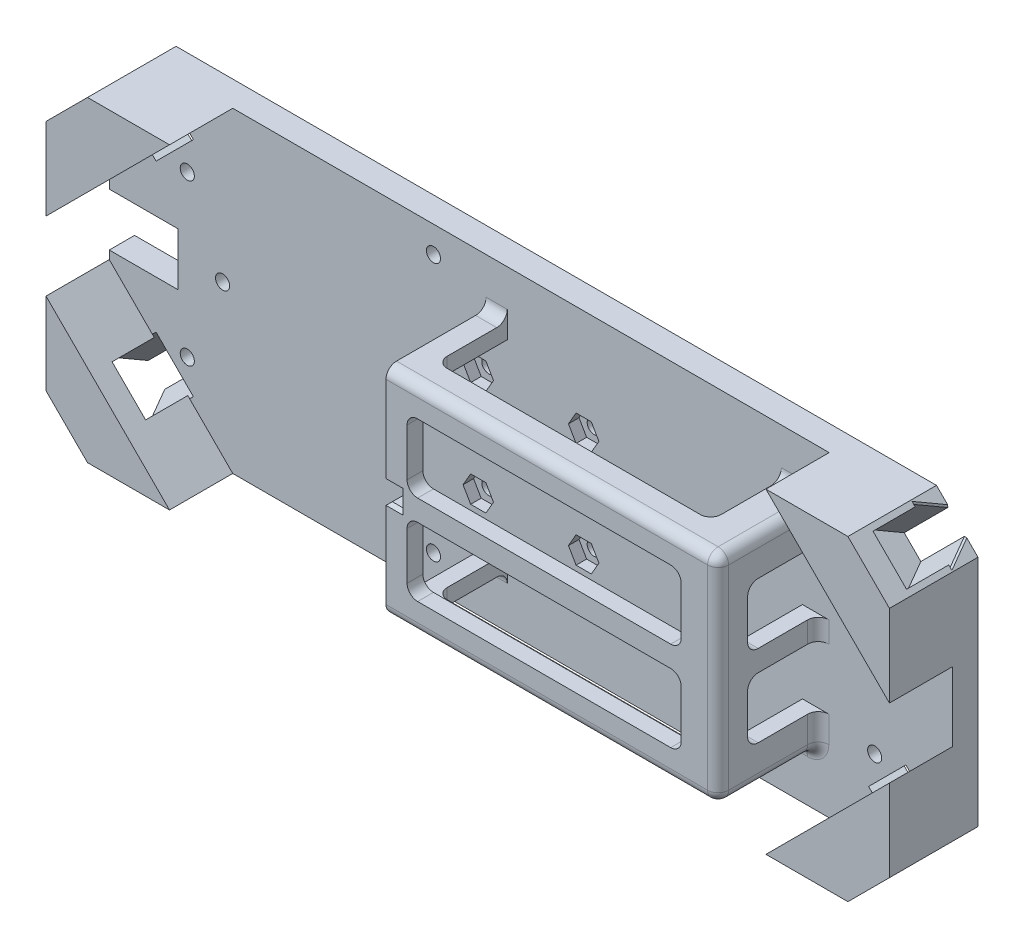
SolidWorks part; units mm, degrees
ref_plane "Front Plane" through (0, 0, 0) normal (0, 0, 1) x (1, 0, 0)
ref_plane "Top Plane" through (0, 0, 0) normal (0, 1, 0) x (1, 0, 0)
ref_plane "Right Plane" through (0, 0, 0) normal (1, 0, 0) x (0, 0, -1)
sketch "Sketch1" plane through (10.8587, 0, 0) normal (0, 0, 1) x (1, 0, 0)
  line L0 (-52.705, 21.59) -> (48.895, 21.59)
  line L1 (52.705, -25.4) -> (-52.705, -25.4)
  line L2 (52.705, -25.4) -> (52.705, 25.4)
  line L3 (52.705, 25.4) -> (-52.705, 25.4)
  line L4 (-52.705, -25.4) -> (-52.705, 25.4)
  line L5 (52.705, -25.4) -> (-52.705, 25.4) construction
  line L6 (52.705, 25.4) -> (-52.705, -25.4) construction
  line L7 (48.895, 21.59) -> (48.895, -22.86)
  line L8 (48.895, -22.86) -> (-52.705, -22.86)
  line L9 (-52.705, 13.97) -> (-6.985, 13.97)
  line L10 (-6.985, 13.97) -> (-6.985, -6.35)
  line L11 (-6.985, -6.35) -> (-52.705, -6.35)
  point P0 (0, 0)
  dimension "D1" = 105.41
  dimension "D2" = 50.8
  dimension "D3" = 101.6
  dimension "D4" = 44.45
  dimension "D5" = 3.81
  dimension "D6" = 45.72
  dimension "D7" = 20.32
  dimension "D8" = 7.62
extrude "Boss-Extrude1" add sketch "Sketch1" along normal blind 27.432 contours L7 L8 L4 L1 L2 L3 L0 region at (-40.6761, 23.495, 0)
extrude "Boss-Extrude2" add sketch "Sketch1<3>" along normal blind 5.08 contours L10 L11 L4 L8 L7 L0 L9 region at (16.19, -1.7862, 0)
sketch "Sketch1<3>" plane through (10.8587, 0, 0) normal (0, 0, 1) x (1, 0, 0) same geometry as "Sketch1"
sketch "Sketch4" plane through (10.8587, 0, 5.08) normal (0, 0, 1) x (1, 0, 0)
  line L0 (-52.705, 21.59) -> (48.895, 21.59) construction
  line L1 (-44.7859, 21.59) -> (-47.9241, 21.59)
  line L2 (-47.9241, 21.59) -> (-49.4932, 18.8722)
  line L3 (-49.4932, 18.8722) -> (-47.9241, 16.1544)
  line L4 (-47.9241, 16.1544) -> (-44.7859, 16.1544)
  line L5 (-44.7859, 16.1544) -> (-43.2168, 18.8722)
  line L6 (-43.2168, 18.8722) -> (-44.7859, 21.59)
  line L7 (-52.705, 13.97) -> (-52.705, 21.59) construction
  line L8 (-13.3987, 22.7847) -> (-13.3987, -11.3368) construction
  line L9 (21.1266, 16.1544) -> (17.9884, 16.1544)
  line L10 (17.9884, 16.1544) -> (16.4193, 18.8722)
  line L11 (16.4193, 18.8722) -> (17.9884, 21.59)
  line L12 (17.9884, 21.59) -> (21.1266, 21.59)
  line L13 (21.1266, 21.59) -> (22.6958, 18.8722)
  line L14 (22.6958, 18.8722) -> (21.1266, 16.1544)
  line L15 (0, 0) -> (10.9329, 0) construction
  line L16 (22.6958, -18.8722) -> (21.1266, -16.1544)
  line L17 (21.1266, -21.59) -> (22.6958, -18.8722)
  line L18 (17.9884, -21.59) -> (21.1266, -21.59)
  line L19 (16.4193, -18.8722) -> (17.9884, -21.59)
  line L20 (17.9884, -16.1544) -> (16.4193, -18.8722)
  line L21 (21.1266, -16.1544) -> (17.9884, -16.1544)
  line L22 (-49.4932, -18.8722) -> (-47.9241, -16.1544)
  line L23 (-47.9241, -21.59) -> (-49.4932, -18.8722)
  line L24 (-43.2168, -18.8722) -> (-44.7859, -21.59)
  line L25 (-44.7859, -16.1544) -> (-43.2168, -18.8722)
  line L26 (-47.9241, -16.1544) -> (-44.7859, -16.1544)
  line L27 (-44.7859, -21.59) -> (-47.9241, -21.59)
  circle A0 centre (-46.355, 18.8722) radius 2.7178 construction
  circle A1 centre (-46.355, 18.8722) radius 1.524
  circle A2 centre (19.5575, 18.8722) radius 1.524
  circle A3 centre (-46.355, -18.8722) radius 1.524
  circle A4 centre (19.5575, -18.8722) radius 1.524
  dimension "D4" = 3.048
  dimension "D1" = 5.4356
  dimension "D2" = 6.35
  dimension "D3" = 2.54
extrude "Cut-Extrude1" cut sketch "Sketch4" against normal blind 2.286 contours L5 L6 L14 L2 L3 L4 A1 | L14 L13 L11 L10 L9 A2 | L26 L22 L23 L12 L24 L25 A3 | L16 L21 L20 L19 L12 L17 A4 region at (-33.2145, 20.1896, 5.08) region at (30.4163, 16.2374, 5.08) region at (32.698, -20.1896, 5.08) region at (-37.778, -17.5548, 5.08)
extrude "Cut-Extrude2" cut sketch "Sketch4<4>" against normal through all contours A1 | A2 | A3 | A4 region at (-35.4963, 18.8722, 5.08) region at (30.4163, 18.8722, 5.08) region at (-35.4963, -18.8722, 5.08) region at (30.4163, -18.8722, 5.08)
sketch "Sketch4<4>" plane through (10.8587, 0, 5.08) normal (0, 0, 1) x (1, 0, 0) same geometry as "Sketch4"
sketch "Sketch7" plane through (10.8587, 0, 27.432) normal (0, 0, 1) x (1, 0, 0)
  line L0 (0, 0) -> (-46.355, 0) construction
  line L1 (-52.705, 25.4) -> (52.705, 25.4)
  line L2 (-52.705, 25.4) -> (-52.705, 6.35)
  line L3 (-52.705, -25.4) -> (52.705, -25.4)
  line L4 (52.705, 25.4) -> (52.705, -25.4)
  line L5 (-52.705, 6.35) -> (-46.355, 6.35)
  line L7 (-52.705, -6.35) -> (-46.355, -6.35)
  line L8 (-46.355, 6.35) -> (-46.355, -6.35)
  line L9 (-52.705, -6.35) -> (-52.705, -25.4)
  line L10 (-28.575, 0) -> (-1035.3573, 0) construction
  point P11 (-46.355, 0)
  dimension "D1" = 12.7
  dimension "D2" = 6.35
extrude "Boss-Extrude3" add sketch "Sketch7" along normal blind 3.81
fillet "Fillet1" radius 2.54 5 edges at (10.8587, -25.4, 31.242) (63.5637, -25.4, 15.621) (63.5637, 0, 31.242) (63.5637, 25.4, 15.621) (10.8587, 25.4, 31.242)
chamfer "Chamfer3" distance 1.27 angle 45 9 edges at (-41.8463, 21.59, 16.256) (-41.8463, -22.86, 16.256) (-41.8463, 13.97, 27.432) (-41.8463, -14.605, 27.432) (-41.8463, -6.35, 29.337) (-38.6713, -6.35, 31.242) (-35.4963, 0, 31.242) (-38.6713, 6.35, 31.242) (-41.8463, 6.35, 29.337)
chamfer "Chamfer4" distance 0.254 angle 45 4 edges at (-33.9723, -18.8722, 0) (31.9403, -18.8722, 0) (-33.9723, 18.8722, 0) (31.9403, 18.8722, 0)
sketch "Sketch8" plane through (10.8587, 0, 5.08) normal (0, 0, 1) x (1, 0, 0)
  line L0 (-52.705, -7.62) -> (-52.705, -22.86) construction
  line L1 (48.895, 21.59) -> (-52.705, 21.59)
  line L2 (48.895, 21.59) -> (48.895, -22.86)
  line L3 (48.895, -22.86) -> (-52.705, -22.86)
  line L4 (-52.705, 21.59) -> (-52.705, -22.86)
  line L5 (48.895, -22.86) -> (-51.435, -22.86) construction
extrude "Cut-Extrude3" cut sketch "Sketch8" against normal up to surface (5.08 mm away) up to face at (-33.7183, -18.8722, 0)
chamfer "Chamfer5" distance 1.27 angle 45 2 edges at (-41.8463, -22.86, 2.54) (-41.8463, 21.59, 2.54)
sketch "Sketch9" plane through (10.8587, 0, 0) normal (0, 0, -1) x (-1, 0, 0)
  line L0 (-90.7413, 28.1) -> (-80.7413, 38.1)
  line L1 (-80.7413, -38.1) -> (102.4587, -38.1)
  line L2 (-90.7413, -28.1) -> (-90.7413, 28.1)
  line L3 (-80.7413, 38.1) -> (102.4587, 38.1)
  line L4 (112.4587, -28.1) -> (112.4587, 28.1)
  line L5 (-90.7413, -38.1) -> (112.4587, 38.1) construction
  line L6 (-90.7413, 38.1) -> (112.4587, -38.1) construction
  line L7 (-90.7413, -28.1) -> (-80.7413, -38.1)
  line L8 (102.4587, 38.1) -> (112.4587, 28.1)
  line L9 (102.4587, -38.1) -> (112.4587, -28.1)
  point P0 (10.8587, 0)
  dimension "D1" = 203.2
  dimension "D2" = 76.2
extrude "Boss-Extrude4" add sketch "Sketch9" along normal blind 6.096
fillet "Fillet2" radius 1.27 5 edges at (9.5887, -25.4, 0) (62.8198, -24.6561, 0) (63.5637, 0, 0) (62.8198, 24.6561, 0) (9.5887, 25.4, 0)
sketch "Sketch11" plane through (0, 0, 0) normal (0, 0, 1) x (1, 0, 0)
  line L0 (-101.6, 28.1) -> (-91.6, 38.1)
  line L1 (-91.6, 38.1) -> (-84.9257, 38.1)
  line L4 (-101.6, -28.1) -> (-101.6, 28.1) construction
  line L5 (-101.6, 21.4257) -> (-101.6, 28.1)
  line L6 (0, 0) -> (0, 53.0626) construction
  line L7 (-1000, 0) -> (0, 0) construction
  line L25 (-76.5885, 29.7628) -> (-93.2628, 13.0885)
  line L26 (-84.9257, 38.1) -> (-76.5885, 29.7628)
  line L28 (-101.6, 21.4257) -> (-93.2628, 13.0885)
  line L54 (0, -17.1831) -> (0, 17.1831) construction
  line L55 (84.9257, 38.1) -> (76.5885, 29.7628)
  line L56 (91.6, 38.1) -> (84.9257, 38.1)
  line L57 (101.6, 28.1) -> (91.6, 38.1)
  line L58 (101.6, 21.4257) -> (101.6, 28.1)
  line L59 (101.6, 21.4257) -> (93.2628, 13.0885)
  line L60 (76.5885, 29.7628) -> (93.2628, 13.0885)
  line L61 (17.1831, 0) -> (-17.1831, 0) construction
  line L62 (91.6, -38.1) -> (84.9257, -38.1)
  line L63 (101.6, -28.1) -> (91.6, -38.1)
  line L64 (101.6, -21.4257) -> (101.6, -28.1)
  line L65 (101.6, -21.4257) -> (93.2628, -13.0885)
  line L66 (76.5885, -29.7628) -> (93.2628, -13.0885)
  line L67 (84.9257, -38.1) -> (76.5885, -29.7628)
  line L68 (-84.9257, -38.1) -> (-76.5885, -29.7628)
  line L69 (-91.6, -38.1) -> (-84.9257, -38.1)
  line L70 (-101.6, -28.1) -> (-91.6, -38.1)
  line L71 (-101.6, -21.4257) -> (-101.6, -28.1)
  line L72 (-101.6, -21.4257) -> (-93.2628, -13.0885)
  line L73 (-76.5885, -29.7628) -> (-93.2628, -13.0885)
  dimension "D1" = 16.51
  dimension "D2" = 8.3372
extrude "Boss-Extrude5" [suppressed] add sketch "Sketch11" along normal blind 19.05
sketch "Sketch13" plane through (-64.85, 64.85, 0) normal (-0.7071, 0.7071, 0) x (0, 0, 1)
  line L0 (-6.096, -44.9013) -> (-6.096, -42.0708)
  line L1 (-6.096, -51.9723) -> (-6.096, -37.8302) construction
  line L2 (-6.096, -42.0708) -> (0, -38.5513)
  line L3 (0, -38.5513) -> (0, -51.2513)
  line L4 (0, -51.2513) -> (-6.096, -47.7318)
  line L5 (-6.096, -47.7318) -> (-6.096, -44.9013)
  dimension "D1" = 6.096
  dimension "D2" = 120
  dimension "D3" = 120
  dimension "D4" = 12.7
extrude "Cut-Extrude4" cut sketch "Sketch13" against normal blind 15.24
mirror "Mirror2" about plane through (0, 0, 0) normal (0, 1, 0) of "Cut-Extrude4"
mirror "Mirror3" about plane through (0, 0, 0) normal (1, 0, 0) of "Cut-Extrude4", "Mirror2"
chamfer "Chamfer7" distance 0.381 angle 45 8 edges at (99.8458, -29.8542, -3.048) (93.3542, -36.3458, -3.048) (93.3542, 36.3458, -3.048) (99.8458, 29.8542, -3.048) (-93.3542, 36.3458, -3.048) (-99.8458, 29.8542, -3.048) (-93.3542, -36.3458, -3.048) (-99.8458, -29.8542, -3.048)
sketch "Sketch17" [suppressed] plane through (0, 0, 19.05) normal (0, 0, 1) x (1, 0, 0)
  line L0 (-96.6, 33.1) -> (-92.1099, 37.5901)
  line L1 (-91.6, 38.1) -> (-101.6, 28.1) construction
  line L3 (20.6756, 0) -> (-20.6756, 0) construction
  line L6 (-80.4355, -25.9158) -> (-89.4158, -16.9355)
  line L8 (-101.0901, 28.6099) -> (-96.6, 33.1)
  line L10 (-92.1099, -37.5901) -> (-80.4355, -25.9158)
  line L30 (-92.1099, 37.5901) -> (-80.4355, 25.9158)
  line L31 (-93.2628, 13.0885) -> (-76.5885, 29.7628) construction
  line L32 (-80.4355, 25.9158) -> (-89.4158, 16.9355)
  line L33 (-89.4158, 16.9355) -> (-101.0901, 28.6099)
  line L34 (-96.6, -33.1) -> (-92.1099, -37.5901)
  line L35 (-101.0901, -28.6099) -> (-96.6, -33.1)
  line L36 (-89.4158, -16.9355) -> (-101.0901, -28.6099)
  line L37 (0, -20.6756) -> (0, 20.6756) construction
  line L38 (92.1099, -37.5901) -> (80.4355, -25.9158)
  line L39 (96.6, -33.1) -> (92.1099, -37.5901)
  line L40 (101.0901, -28.6099) -> (96.6, -33.1)
  line L41 (89.4158, -16.9355) -> (101.0901, -28.6099)
  line L42 (80.4355, -25.9158) -> (89.4158, -16.9355)
  line L43 (80.4355, 25.9158) -> (89.4158, 16.9355)
  line L44 (92.1099, 37.5901) -> (80.4355, 25.9158)
  line L45 (96.6, 33.1) -> (92.1099, 37.5901)
  line L46 (101.0901, 28.6099) -> (96.6, 33.1)
  line L47 (89.4158, 16.9355) -> (101.0901, 28.6099)
  dimension "D1" = 12.7
extrude "Cut-Extrude7" [suppressed] cut sketch "Sketch17" against normal blind 10.922
sketch "Sketch18" [suppressed] plane through (0, 0, 8.128) normal (0, 0, 1) x (1, 0, 0)
  line L0 (-92.1099, 37.5901) -> (-101.0901, 28.6099) construction
  line L1 (-80.4355, 25.9158) -> (-92.1099, 37.5901) construction
  circle A0 centre (-89.4158, 25.9158) radius 1.778
  dimension "D1" = 3.556
  dimension "D2" = 10.16
  dimension "D3" = 6.35
extrude "Cut-Extrude8" [suppressed] cut sketch "Sketch18" against normal up to surface (8.382 mm away) up to face at (0, 0, 0)
mirror "Mirror6" [suppressed] about plane through (0, 0, 0) normal (0, 1, 0)
mirror "Mirror7" [suppressed] about plane through (0, 0, 0) normal (1, 0, 0)
sketch "Sketch19" plane through (0, 0, 31.242) normal (0, 0, 1) x (1, 0, 0)
  line L1 (-67.9348, -33.6729) -> (67.9348, -33.6729)
  line L2 (-67.9348, -33.6729) -> (-67.9348, 33.6729)
  line L3 (-67.9348, 33.6729) -> (67.9348, 33.6729)
  line L4 (67.9348, -33.6729) -> (67.9348, 33.6729)
  line L5 (-67.9348, -33.6729) -> (67.9348, 33.6729) construction
  line L6 (-67.9348, 33.6729) -> (67.9348, -33.6729) construction
  point P0 (0, 0)
extrude "Cut-Extrude9" cut sketch "Sketch19" against normal up to surface (31.242 mm away) up to face at (0, 0, 0)
sketch "Sketch20" plane through (0, 0, 0) normal (0, 0, 1) x (1, 0, 0)
  line L0 (65.405, 22.86) -> (65.405, -21.59)
  line L1 (65.405, -21.59) -> (-10.795, -21.59)
  line L2 (65.405, 22.86) -> (-10.795, 22.86)
  line L3 (-10.795, 22.86) -> (-10.795, 26.67)
  line L4 (-10.795, 26.67) -> (69.215, 26.67)
  line L5 (69.215, 26.67) -> (69.215, -25.4)
  line L6 (69.215, -25.4) -> (-10.795, -25.4)
  line L7 (-10.795, -25.4) -> (-10.795, -21.59)
  line L8 (101.6, 28.1) -> (101.6, -28.1) construction
  line L9 (91.6, -38.1) -> (-91.6, -38.1) construction
  dimension "D1" = 52.07
  dimension "D2" = 44.45
  dimension "D3" = 3.81
  dimension "D4" = 80.01
  dimension "D5" = 76.2
  dimension "D6" = 32.385
  dimension "D7" = 12.7
extrude "Boss-Extrude6" add sketch "Sketch20" along normal blind 20.32
sketch "Sketch21" plane through (0, 0, 20.32) normal (0, 0, 1) x (1, 0, 0)
  line L1 (-10.795, 26.67) -> (69.215, 26.67)
  line L2 (-10.795, 26.67) -> (-10.795, -25.4)
  line L3 (-10.795, -25.4) -> (69.215, -25.4)
  line L4 (69.215, 26.67) -> (69.215, -25.4)
extrude "Boss-Extrude7" add sketch "Sketch21" along normal blind 3.81
fillet "Fillet3" radius 2.54 8 edges at (29.21, 26.67, 0) (69.215, 0.635, 0) (29.21, 26.67, 24.13) (69.215, 26.67, 12.065) (69.215, 0.635, 24.13) (69.215, -25.4, 12.065) (29.21, -25.4, 0) (29.21, -25.4, 24.13)
chamfer "Chamfer8" distance 1.27 angle 45 3 edges at (-10.795, -21.59, 10.16) (-10.795, 22.86, 10.16) (-10.795, 0.635, 20.32)
chamfer "Chamfer9" [suppressed] distance 0.254 angle 45
sketch "Sketch22" [suppressed] plane through (0, 0, -0.254) normal (0, 0, -1) x (-1, 0, 0)
  line L0 (-91.6432, -38.0568) -> (-101.5568, -28.1432) construction
  line L1 (-85.0164, -25.9158) -> (-87.2161, -22.1058)
  line L2 (-87.2161, -22.1058) -> (-91.6155, -22.1058)
  line L3 (-91.6155, -22.1058) -> (-93.8152, -25.9158)
  line L4 (-93.8152, -25.9158) -> (-91.6155, -29.7258)
  line L5 (-91.6155, -29.7258) -> (-87.2161, -29.7258)
  line L6 (-87.2161, -29.7258) -> (-85.0164, -25.9158)
  circle A0 centre (-89.4158, -25.9158) radius 3.81 construction
  circle A1 centre (-89.4158, -25.9158) radius 1.778 construction
  dimension "D1" = 7.62
  dimension "D2" = 10.16
  dimension "D3" = 0
extrude "Cut-Extrude10" [suppressed] cut sketch "Sketch22" against normal blind 3.302
mirror "Mirror8" [suppressed] about plane through (0, 0, 0) normal (0, 1, 0)
mirror "Mirror9" [suppressed] about plane through (0, 0, 0) normal (1, 0, 0)
sketch "Sketch23" plane through (0, 0, 0) normal (0, 0, 1) x (1, 0, 0)
  line L16 (90.3138, -17.8336) -> (100.8207, -28.3405)
  line L18 (-91.6, -38.1) -> (91.6, -38.1)
  line L19 (100.8207, -28.3405) -> (101.4012, -28.2988)
  line L20 (100.8207, -28.3405) -> (101.4012, -28.2988)
  line L21 (101.4012, -28.2988) -> (101.6, -28.1)
  line L22 (101.6, -28.1) -> (101.6, 28.1)
  line L23 (101.4012, -28.2988) -> (101.6, -28.1)
  line L24 (101.6, 28.1) -> (101.4012, 28.2988)
  line L25 (101.6, 28.1) -> (101.4012, 28.2988)
  line L26 (91.6, 38.1) -> (-91.6, 38.1)
  line L27 (101.4012, 28.2988) -> (100.8207, 28.3405)
  line L28 (101.4012, 28.2988) -> (100.8207, 28.3405)
  line L29 (90.3138, -17.8336) -> (100.8207, -28.3405)
  line L30 (-101.6, 28.1) -> (-101.6, -28.1)
  line L34 (-91.6, -38.1) -> (91.6, -38.1)
  line L38 (101.6, -28.1) -> (101.6, 28.1)
  line L42 (91.6, 38.1) -> (-91.6, 38.1)
  line L46 (-101.6, 28.1) -> (-101.6, -28.1)
  line L56 (91.8405, 37.3207) -> (91.7988, 37.9012)
  line L57 (91.8405, 37.3207) -> (91.7988, 37.9012)
  line L58 (91.7988, 37.9012) -> (91.6, 38.1)
  line L59 (91.7988, 37.9012) -> (91.6, 38.1)
  line L60 (-91.6, 38.1) -> (-91.7988, 37.9012)
  line L61 (-91.6, 38.1) -> (-91.7988, 37.9012)
  line L62 (-91.7988, 37.9012) -> (-91.8405, 37.3207)
  line L63 (-91.7988, 37.9012) -> (-91.8405, 37.3207)
  line L64 (100.8207, 28.3405) -> (90.3138, 17.8336)
  line L66 (-100.8207, 28.3405) -> (-101.4012, 28.2988)
  line L67 (-100.8207, 28.3405) -> (-101.4012, 28.2988)
  line L68 (-101.4012, 28.2988) -> (-101.6, 28.1)
  line L69 (-101.4012, 28.2988) -> (-101.6, 28.1)
  line L70 (-101.6, -28.1) -> (-101.4012, -28.2988)
  line L71 (-101.6, -28.1) -> (-101.4012, -28.2988)
  line L72 (-101.4012, -28.2988) -> (-100.8207, -28.3405)
  line L73 (-101.4012, -28.2988) -> (-100.8207, -28.3405)
  line L74 (100.8207, 28.3405) -> (90.3138, 17.8336)
  line L76 (-91.8405, -37.3207) -> (-91.7988, -37.9012)
  line L77 (-91.8405, -37.3207) -> (-91.7988, -37.9012)
  line L78 (-91.7988, -37.9012) -> (-91.6, -38.1)
  line L79 (-91.7988, -37.9012) -> (-91.6, -38.1)
  line L80 (91.6, -38.1) -> (91.7988, -37.9012)
  line L81 (91.6, -38.1) -> (91.7988, -37.9012)
  line L82 (91.7988, -37.9012) -> (91.8405, -37.3207)
  line L83 (91.7988, -37.9012) -> (91.8405, -37.3207)
  line L92 (90.3138, 17.8336) -> (81.3336, 26.8138)
  line L93 (90.3138, 17.8336) -> (81.3336, 26.8138)
  line L94 (81.3336, 26.8138) -> (91.8405, 37.3207)
  line L95 (81.3336, 26.8138) -> (91.8405, 37.3207)
  line L96 (-91.8405, 37.3207) -> (-81.3336, 26.8138)
  line L97 (-91.8405, 37.3207) -> (-81.3336, 26.8138)
  line L98 (-81.3336, 26.8138) -> (-90.3138, 17.8336)
  line L99 (-81.3336, 26.8138) -> (-90.3138, 17.8336)
  line L100 (-90.3138, 17.8336) -> (-100.8207, 28.3405)
  line L101 (-90.3138, 17.8336) -> (-100.8207, 28.3405)
  line L102 (-100.8207, -28.3405) -> (-90.3138, -17.8336)
  line L103 (-100.8207, -28.3405) -> (-90.3138, -17.8336)
  line L104 (-90.3138, -17.8336) -> (-81.3336, -26.8138)
  line L105 (-90.3138, -17.8336) -> (-81.3336, -26.8138)
  line L106 (-81.3336, -26.8138) -> (-91.8405, -37.3207)
  line L107 (-81.3336, -26.8138) -> (-91.8405, -37.3207)
  line L108 (91.8405, -37.3207) -> (81.3336, -26.8138)
  line L109 (91.8405, -37.3207) -> (81.3336, -26.8138)
  line L110 (81.3336, -26.8138) -> (90.3138, -17.8336)
  line L111 (81.3336, -26.8138) -> (90.3138, -17.8336)
  dimension "D1" = 0
sketch "Sketch24" plane through (0, 0, 0) normal (0, 0, 1) x (1, 0, 0)
  line L10 (-90.7628, 19.1806) -> (-101.6, 8.3434)
  line L11 (-101.6, -28.1) -> (-101.6, 28.1) construction
  line L12 (-101.6, 8.3434) -> (-101.6, 28.1)
  line L13 (-101.6, 28.1) -> (-100.6411, 29.0589)
  line L14 (-100.6411, 29.0589) -> (-90.7628, 19.1806)
  line L15 (-92.5589, 37.1411) -> (-91.6, 38.1)
  line L16 (-91.6, 38.1) -> (-71.8434, 38.1)
  line L17 (-91.6, 38.1) -> (91.6, 38.1) construction
  line L18 (-71.8434, 38.1) -> (-82.6806, 27.2628)
  line L19 (-82.6806, 27.2628) -> (-92.5589, 37.1411)
extrude "Boss-Extrude8" add sketch "Sketch24" along normal blind 10.16
sketch "Sketch26" plane through (0, 0, 10.16) normal (0, 0, 1) x (1, 0, 0)
  line L0 (-101.6, 8.3434) -> (-71.8434, 38.1)
  line L1 (-71.8434, 38.1) -> (-91.6, 38.1)
  line L2 (-91.6, 38.1) -> (-101.6, 28.1)
  line L3 (-101.6, 28.1) -> (-101.6, 8.3434)
extrude "Boss-Extrude10" add sketch "Sketch26" along normal blind 5.08
mirror "Mirror12" about plane through (0, 0, 0) normal (0, 1, 0) of "Boss-Extrude8", "Boss-Extrude10"
mirror "Mirror13" about plane through (0, 0, 0) normal (1, 0, 0) of "Mirror12"
sketch "Sketch27" plane through (0, 0, 0) normal (0, 0, 1) x (1, 0, 0)
  circle A0 centre (-23.495, 31.75) radius 1.7
  circle A1 centre (-23.495, -30.48) radius 1.7
  dimension "D1" = 3.4
extrude "Cut-Extrude11" cut sketch "Sketch27" against normal up to next
sketch "Sketch28" plane through (0, 0, -6.096) normal (0, 0, -1) x (-1, 0, 0)
  circle A0 centre (23.495, -30.48) radius 3.302
  circle A1 centre (23.495, 31.75) radius 3.302
  dimension "D1" = 6.604
extrude "Cut-Extrude12" cut sketch "Sketch28" against normal blind 3.302
sketch "Sketch29" plane through (0, 0, 24.13) normal (0, 0, 1) x (1, 0, 0)
  line L0 (-10.795, 24.13) -> (-10.795, -22.86) construction
  line L1 (-5.715, 19.685) -> (60.325, 19.685)
  line L2 (-5.715, 19.685) -> (-5.715, 3.175)
  line L3 (-5.715, -18.415) -> (60.325, -18.415)
  line L4 (60.325, 19.685) -> (60.325, 3.175)
  line L6 (66.675, -22.86) -> (66.675, 24.13) construction
  line L7 (-10.795, -22.86) -> (66.675, -22.86) construction
  line L8 (-5.715, -1.905) -> (-5.715, -18.415)
  line L9 (-5.715, 3.175) -> (60.325, 3.175)
  line L11 (-5.715, -1.905) -> (60.325, -1.905)
  line L13 (60.325, -1.905) -> (60.325, -18.415)
  dimension "D1" = 38.1
  dimension "D2" = 6.35
  dimension "D3" = 5.08
  dimension "D4" = 4.445
  dimension "D5" = 5.08
extrude "Cut-Extrude13" cut sketch "Sketch29" against normal up to next
sketch "Sketch30" plane through (0, -25.4, 0) normal (0, -1, 0) x (1, 0, 0)
  line L0 (71.8434, 0) -> (-71.8434, 0) construction
  line L1 (-5.715, 0) -> (60.325, 0)
  line L2 (-5.715, 0) -> (-5.715, 17.018)
  line L3 (-5.715, 17.018) -> (60.325, 17.018)
  line L4 (60.325, 0) -> (60.325, 17.018)
  line L5 (-10.795, 21.59) -> (-10.795, 2.54) construction
  line L6 (66.675, 2.54) -> (66.675, 21.59) construction
  line L7 (66.675, 21.59) -> (-10.795, 21.59) construction
  dimension "D1" = 5.08
  dimension "D2" = 6.35
  dimension "D3" = 4.572
extrude "Cut-Extrude14" cut sketch "Sketch30" against normal through all
sketch "Sketch31" plane through (69.215, 0, 0) normal (1, 0, 0) x (0, 0, -1)
  line L0 (-21.59, 24.13) -> (-21.59, -22.86) construction
  line L1 (-17.018, 17.78) -> (0, 17.78)
  line L2 (-17.018, 17.78) -> (-17.018, 3.175)
  line L3 (-17.018, -16.51) -> (0, -16.51)
  line L4 (0, 17.78) -> (0, 3.175)
  line L5 (0, 8.3434) -> (0, -8.3434) construction
  line L6 (-2.54, 24.13) -> (-21.59, 24.13) construction
  line L7 (-21.59, -22.86) -> (-2.54, -22.86) construction
  line L9 (-17.018, -1.905) -> (0, -1.905)
  line L11 (-17.018, 3.175) -> (0, 3.175)
  line L15 (-17.018, -1.905) -> (-17.018, -16.51)
  line L16 (0, -1.905) -> (0, -16.51)
  point P12 (-17.018, 0.635)
  dimension "D1" = 4.572
  dimension "D2" = 0
  dimension "D3" = 6.35
  dimension "D4" = 6.35
  dimension "D5" = 5.08
extrude "Cut-Extrude15" cut sketch "Sketch31" against normal up to next
sketch "Sketch32" plane through (0, -25.4, 0) normal (0, 1, 0) x (1, 0, 0)
  line L1 (-5.715, 0) -> (60.325, 0)
  line L2 (-5.715, 0) -> (-5.715, -2.54)
  line L3 (-5.715, -2.54) -> (60.325, -2.54)
  line L4 (60.325, 0) -> (60.325, -2.54)
extrude "Cut-Extrude16" cut sketch "Sketch32" against normal through all
sketch "Sketch33" plane through (69.215, 0, 0) normal (-1, 0, 0) x (0, 0, 1)
  line L0 (17.018, 17.78) -> (0, 17.78) construction
  line L1 (2.6099, 17.78) -> (0, 17.78)
  line L2 (2.6099, 17.78) -> (2.6099, -16.51)
  line L3 (2.6099, -16.51) -> (0, -16.51)
  line L4 (0, 17.78) -> (0, -16.51)
  line L5 (0, -16.51) -> (17.018, -16.51) construction
  point P6 (1.3049, -16.51)
  dimension "D1" = 0
  dimension "D2" = 0
extrude "Cut-Extrude17" cut sketch "Sketch33" against normal blind 3.302
sketch "Sketch34" plane through (0, 0, 0) normal (0, 0, 1) x (1, 0, 0)
  circle A0 centre (-74.295, 0.635) radius 1.7
extrude "Cut-Extrude18" cut sketch "Sketch34" against normal through all
sketch "Sketch35" plane through (0, 0, -6.096) normal (0, 0, -1) x (-1, 0, 0)
  circle A0 centre (74.295, 0.635) radius 3.302
  dimension "D1" = 6.604
extrude "Cut-Extrude19" cut sketch "Sketch35" against normal blind 3.302
fillet "Fillet4" radius 2.54 17 edges at (-5.715, 3.175, 22.225) (-5.715, -18.415, 22.225) (60.325, 3.175, 22.225) (60.325, -18.415, 22.225) (60.325, -1.905, 22.225) (60.325, 19.685, 22.225) (-5.715, 19.685, 22.225) (-5.715, -1.905, 22.225) (-5.715, -23.495, 17.018) (60.325, -23.495, 17.018) (-5.715, 24.765, 17.018) (60.325, 24.765, 17.018) (67.31, -16.51, 17.018) (67.31, 3.175, 17.018) (67.31, 17.78, 17.018) (67.31, -1.905, 17.018) (69.215, 0.635, 0)
hole_wizard "CBORE for M3 SHCS1" positions "Sketch36" profile "Sketch37" counterbore size "M3" standard "ANSI Metric" end condition up to next
sketch "Sketch36" plane through (0, 0, -6.096) normal (0, 0, -1) x (-1, 0, 0)
  line L0 (-91.6, -38.1) -> (91.6, -38.1) construction
  line L1 (101.6, -28.1) -> (101.6, 28.1) construction
  point P0 (82.804, -19.304)
  dimension "D1" = 18.796
  dimension "D2" = 18.796
sketch "Sketch37" plane through (-82.804, -19.304, -6.096) normal (1, 0, 0) x (0, 1, 0)
  line L0 (0, 0) -> (0, 6.097)
  line L1 (0, 6.097) -> (1.7, 6.097)
  line L3 (1.7, 6.097) -> (1.7, 3)
  line L4 (1.7, 3) -> (3.25, 3)
  line L5 (3.25, 3) -> (3.25, 0)
  line L7 (3.25, 0) -> (0, 0)
  line L11 (0, -6.35) -> (0, 107.95) construction
  dimension "Thru Hole Dia." = 3.4
  dimension "Thru Hole Depth" = 6.097
  dimension "C'Bore Dia." = 6.5
  dimension "C'Bore Depth" = 3
mirror "Mirror14" about plane through (0, 0, 0) normal (0, 1, 0) of "CBORE for M3 SHCS1"
mirror "Mirror15" about plane through (0, 0, 0) normal (1, 0, 0) of "Mirror14"
sketch "Sketch38" plane through (0, 0, -6.096) normal (0, 0, -1) x (-1, 0, 0)
  line L1 (-5.715, -3.81) -> (5.715, -3.81)
  line L2 (-5.715, -3.81) -> (-5.715, 3.81)
  line L3 (-5.715, 3.81) -> (5.715, 3.81)
  line L4 (5.715, -3.81) -> (5.715, 3.81)
  line L5 (-5.715, -3.81) -> (5.715, 3.81) construction
  line L6 (-5.715, 3.81) -> (5.715, -3.81) construction
  point P0 (0, 0)
  dimension "D1" = 11.43
  dimension "D2" = 7.62
extrude "Cut-Extrude20" cut sketch "Sketch38" against normal up to next
chamfer "Chamfer10" distance 0.762 angle 45 4 edges at (0, -3.81, -6.096) (5.715, 0, -6.096) (0, 3.81, -6.096) (-5.715, 0, -6.096)
hole_wizard "M3 Clearance Hole1" positions "Sketch39" profile "Sketch40" hole size "M3" standard "ANSI Metric" end condition up to next
sketch "Sketch39" plane through (0, 0, -6.096) normal (0, 0, -1) x (-1, 0, 0)
  line L0 (16.6243, 0) -> (-16.6243, 0) construction
  line L2 (0, 16.6243) -> (0, -16.6243) construction
  point P0 (12.7, 12.7)
  dimension "D1" = 12.7
  dimension "D2" = 12.7
sketch "Sketch40" plane through (-12.7, 12.7, -6.096) normal (1, 0, 0) x (0, 1, 0)
  line L0 (0, 0) -> (0, 6.097)
  line L1 (0, 6.097) -> (1.7, 6.097)
  line L2 (1.7, 6.097) -> (1.7, 0)
  line L5 (1.7, 0) -> (0, 0)
  line L11 (0, -6.35) -> (0, 107.95) construction
  dimension "Thru Hole Dia." = 3.4
  dimension "Thru Hole Depth" = 6.097
mirror "Mirror16" about plane through (0, 0, 0) normal (0, 1, 0) of "M3 Clearance Hole1"
mirror "Mirror17" about plane through (0, 0, 0) normal (1, 0, 0) of "Mirror16"
sketch "Sketch42" plane through (0, 0, 0) normal (0, 0, 1) x (1, 0, 0)
  line L1 (16.3662, 12.7) -> (14.5331, 15.875)
  line L2 (14.5331, 15.875) -> (10.8669, 15.875)
  line L3 (10.8669, 15.875) -> (9.0338, 12.7)
  line L4 (9.0338, 12.7) -> (10.8669, 9.525)
  line L5 (10.8669, 9.525) -> (14.5331, 9.525)
  line L6 (14.5331, 9.525) -> (16.3662, 12.7)
  circle A0 centre (12.7, 12.7) radius 3.175 construction
  dimension "D1" = 6.35
extrude "Cut-Extrude21" cut sketch "Sketch42" against normal blind 2.54
mirror "Mirror18" about plane through (0, 0, 0) normal (1, 0, 0) of "Cut-Extrude21"
mirror "Mirror19" about plane through (0, 0, 0) normal (0, 1, 0) of "Mirror18"
sketch "Sketch43" plane through (0, 0, 24.13) normal (0, 0, 1) x (1, 0, 0)
  line L0 (-10.795, 24.13) -> (-10.795, -22.86) construction
  line L1 (-14.097, -1.397) -> (-7.493, -1.397)
  line L2 (-14.097, -1.397) -> (-14.097, 2.667)
  line L3 (-14.097, 2.667) -> (-7.493, 2.667)
  line L4 (-7.493, -1.397) -> (-7.493, 2.667)
  line L5 (-14.097, -1.397) -> (-7.493, 2.667) construction
  line L6 (-14.097, 2.667) -> (-7.493, -1.397) construction
  point P0 (-10.795, 0.635)
  dimension "D1" = 6.604
  dimension "D2" = 4.064
extrude "Cut-Extrude22" cut sketch "Sketch43" against normal up to next
chamfer "Chamfer11" distance 0.762 angle 45 5 edges at (-10.795, -1.397, 22.86) (-9.144, -1.397, 24.13) (-7.493, 0.635, 24.13) (-9.144, 2.667, 24.13) (-10.795, 2.667, 22.86)
sketch "Sketch44" plane through (0, 0, 0) normal (0, 0, 1) x (1, 0, 0)
  line L0 (-101.6, -8.3434) -> (-101.6, 8.3434) construction
  line L1 (-118.142, -6.35) -> (-85.058, -6.35)
  line L2 (-118.142, -6.35) -> (-118.142, 6.35)
  line L3 (-118.142, 6.35) -> (-85.058, 6.35)
  line L4 (-85.058, -6.35) -> (-85.058, 6.35)
  line L5 (-118.142, -6.35) -> (-85.058, 6.35) construction
  line L6 (-118.142, 6.35) -> (-85.058, -6.35) construction
  point P0 (-101.6, 0)
  dimension "D1" = 12.7
extrude "Cut-Extrude23" cut sketch "Sketch44" against normal through all
